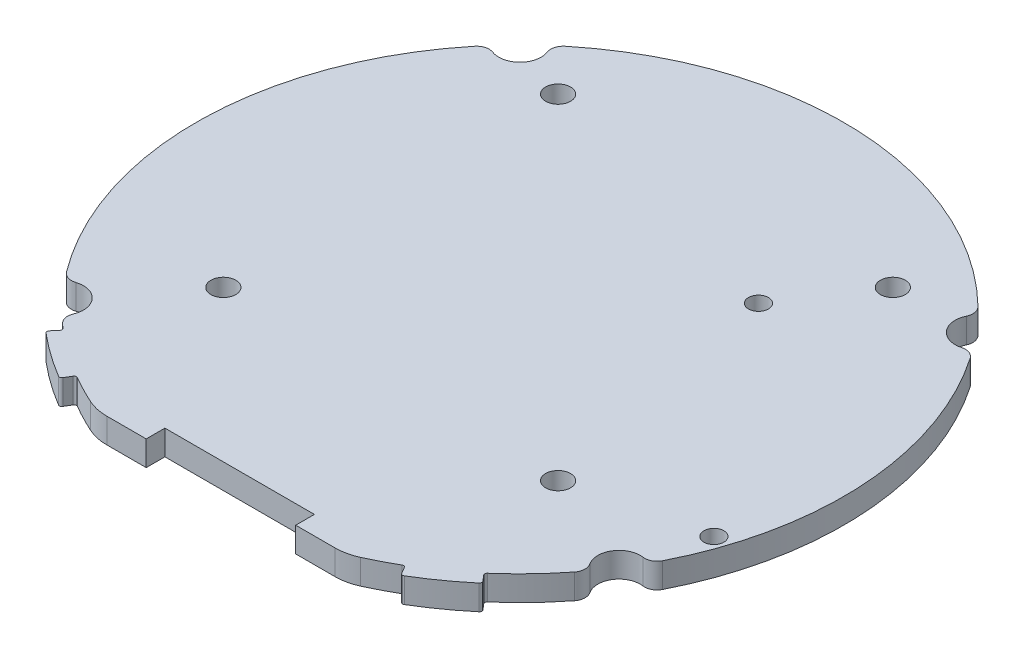
SolidWorks part; units mm, degrees
ref_plane "Front Plane" through (0, 0, 0) normal (0, 0, 1) x (1, 0, 0)
ref_plane "Top Plane" through (0, 0, 0) normal (0, 1, 0) x (1, 0, 0)
ref_plane "Right Plane" through (0, 0, 0) normal (1, 0, 0) x (0, 0, -1)
sketch "Sketch1" plane through (0, 0, 0) normal (0, 1, 0) x (1, 0, 0)
  line L0 (0, 0) -> (0, -5.9322) construction
  circle A0 centre (0, 0) radius 13
  dimension "D1" = 26
extrude "Boss-Extrude1" add sketch "Sketch1" along normal blind 1
sketch "Sketch3" plane through (0, 0, 0) normal (0, 1, 0) x (1, 0, 0)
  line L0 (-5, -12) -> (5, -12)
  line L1 (0, -12) -> (0, 0) construction
  circle A0 centre (0, 0) radius 13 construction
  arc A1 (-5, -12) -> (5, -12) centre (0, 0) ccw
  dimension "D1" = 12
extrude "Cut-Extrude2" cut sketch "Sketch3" along normal up to surface (1 mm away) up to face at (0, 1, 13)
fillet "Fillet1" radius 2 2 edges at (5, 0.5, 12) (-5, 0.5, 12)
sketch "Sketch9" plane through (0, 0, 0) normal (0, 1, 0) x (1, 0, 0)
  point P0 (-7, -9.8)
  dimension "D1" = 9.8
  dimension "D2" = 7
ref_axis "Axis2" through (-7, 0, 9.8) along (0, 1, 0)
sketch "Sketch4" plane through (0, 0, 0) normal (0, -1, 0) x (1, 0, 0)
  circle A0 centre (6.7175, 5.1869) radius 0.5
  circle A1 centre (-6.7175, 5.1869) radius 0.5
  circle A2 centre (-6.7175, -8.2482) radius 0.5
  circle A3 centre (6.7175, -8.2482) radius 0.5
extrude "Cut-Extrude3" cut sketch "Sketch4" against normal up to surface (1 mm away) up to face at (0, 1, 5.727)
sketch "Sketch5" plane through (0, 1, 0) normal (0, 1, 0) x (1, 0, 0)
  line L0 (0, -0.55) -> (0, 0.55) construction
  circle A0 centre (-7, -9.8) radius 1.375
  circle A1 centre (7, -9.8) radius 1.375
  dimension "D3" = 2.75
  dimension "D1" = 7
  dimension "D2" = 9.8
sketch "Sketch6" plane through (0, 0, 0) normal (0, -1, 0) x (1, 0, 0)
  line L0 (0, 0) -> (17.8207, 0) construction
  line L1 (9.9586, -8.3562) -> (0, 0) construction
  line L2 (0, 0) -> (-9.1924, -9.1924) construction
  line L3 (10.9641, 6.9849) -> (0, 0) construction
  line L4 (-9.5846, 8.7827) -> (0, 0) construction
  circle A0 centre (9.9586, -8.3562) radius 0.85
  circle A1 centre (-9.5846, 8.7827) radius 0.85
  circle A2 centre (-9.1924, -9.1924) radius 0.85
  circle A3 centre (10.9641, 6.9849) radius 0.85
  circle A7 centre (0, 0) radius 13 construction
  dimension "D1" = 1.7
  dimension "D2" = 40
  dimension "D4" = 45
  dimension "D5" = 72.5
  dimension "D6" = 42.5
extrude "Cut-Extrude4" cut sketch "Sketch6" against normal blind 10 separate body
fillet "Fillet2" radius 0.5 8 edges at (10.4834, 0.5, -7.6876) (9.3912, 0.5, -8.9892) (-8.572, 0.5, -9.7735) (-9.7735, 0.5, -8.572) (10.4842, 0.5, 7.6865) (11.3971, 0.5, 6.2535) (-8.9902, 0.5, 9.3902) (-10.1381, 0.5, 8.1375)
sketch "Sketch10" plane through (0, 1, 0) normal (0, 1, 0) x (1, 0, 0)
  line L0 (0, 0) -> (-7.5491, -10.5835) construction
  line L1 (-6.598, -11.2012) -> (-6.8518, -11.632)
  line L2 (-8.4428, -9.8853) -> (-8.7675, -10.2655)
  line L3 (0, 0) -> (0, -18.864) construction
  line L4 (8.4428, -9.8853) -> (8.7675, -10.2655)
  line L5 (6.598, -11.2012) -> (6.8518, -11.632)
  arc A1 (-8.4428, -9.8853) -> (-6.598, -11.2012) centre (0, 0) ccw
  arc A2 (-8.7675, -10.2655) -> (-6.8518, -11.632) centre (0, 0) ccw
  arc A3 (6.8518, -11.632) -> (8.7675, -10.2655) centre (0, 0) ccw
  arc A4 (6.598, -11.2012) -> (8.4428, -9.8853) centre (0, 0) ccw
  arc A5 (-8.6753, -9.6819) -> (-5.4158, -11.8182) centre (0, 0) ccw construction
  point P19 (0, 0)
  dimension "D2" = 35.5
  dimension "D3" = 0.5
  dimension "D1" = 5
  dimension "D4" = 2
extrude "Boss-Extrude4" add sketch "Sketch10" against normal up to surface (1 mm away) up to face at (6.7175, 0, -8.7482)
fillet "Fillet4" radius 0.1 8 edges at (-8.4428, 0.5, 9.8853) (-6.598, 0.5, 11.2012) (6.598, 0.5, 11.2012) (8.4428, 0.5, 9.8853) (8.7675, 0.5, 10.2655) (6.8518, 0.5, 11.632) (-6.8518, 0.5, 11.632) (-8.7675, 0.5, 10.2655)
sketch "Sketch11" plane through (0, 0, 0) normal (0, 1, 0) x (1, 0, 0)
  line L0 (4.5826, -12) -> (-4.5826, -12) construction
  line L1 (3, -12.75) -> (-3, -12.75)
  line L2 (3, -12.75) -> (3, -11.25)
  line L3 (3, -11.25) -> (-3, -11.25)
  line L4 (-3, -12.75) -> (-3, -11.25)
  line L5 (3, -12.75) -> (-3, -11.25) construction
  line L6 (3, -11.25) -> (-3, -12.75) construction
  point P0 (0, -12)
  dimension "D1" = 1.5
  dimension "D2" = 6
extrude "Cut-Extrude6" cut sketch "Sketch11" against normal through all and the other way through all
sketch "Sketch12" plane through (0, 1, 0) normal (0, 1, 0) x (1, 0, 0)
  circle A0 centre (4.5711, 5) radius 0.4
  circle A1 centre (11.7828, -4) radius 0.4
  dimension "D1" = 0.8
extrude "Cut-Extrude7" cut sketch "Sketch12" against normal up to surface (1 mm away) up to face at (6.7175, 0, -8.7482)
